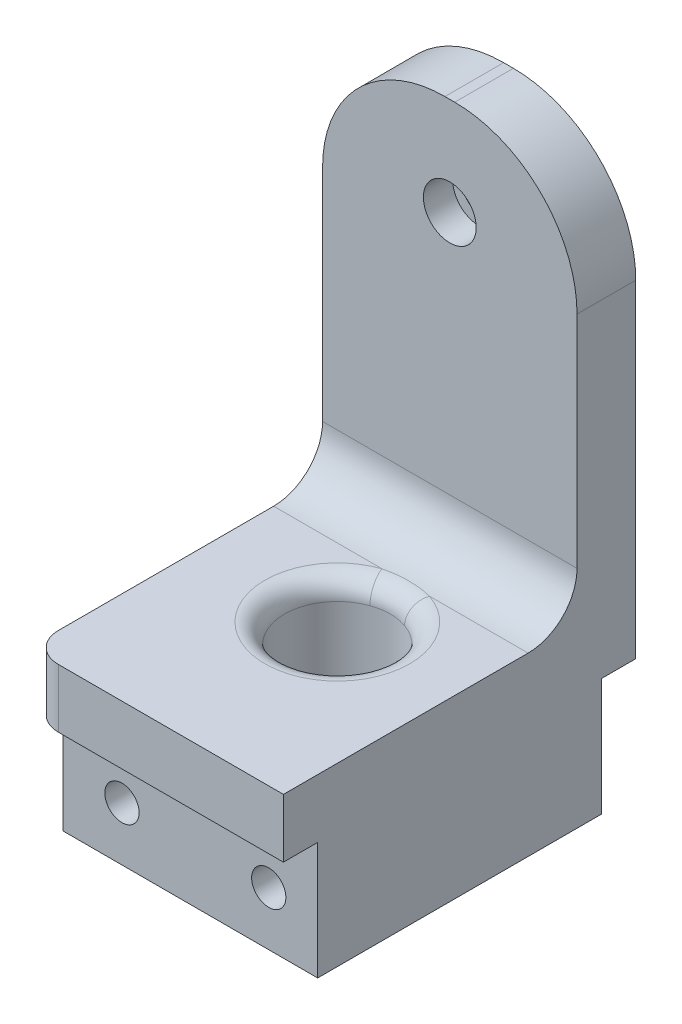
SolidWorks part; units mm, degrees
ref_plane "Front Plane" through (0, 0, 0) normal (0, 0, 1) x (1, 0, 0)
ref_plane "Top Plane" through (0, 0, 0) normal (0, 1, 0) x (1, 0, 0)
ref_plane "Right Plane" through (0, 0, 0) normal (1, 0, 0) x (0, 0, -1)
sketch "Sketch1" plane through (0, -44, 0) normal (0, 1, 0) x (1, 0, 0)
  line L0 (50.2641, 25) -> (50.2641, 28) construction
  line L1 (50.2641, -8) -> (50.2641, 28)
  line L2 (50.2641, -8) -> (27.2641, -8) construction
  line L3 (50.2641, -8) -> (27.2641, -8)
  line L4 (24.2641, -5) -> (24.2641, 25)
  line L5 (27.2641, 28) -> (50.2641, 28)
  arc A0 (27.2641, 28) -> (24.2641, 25) centre (27.2641, 25) ccw construction
  arc A1 (24.2641, -5) -> (27.2641, -8) centre (27.2641, -5) ccw construction
  arc A2 (27.2641, 28) -> (24.2641, 25) centre (27.2641, 25) ccw
  arc A3 (24.2641, -5) -> (27.2641, -8) centre (27.2641, -5) ccw
extrude "Boss-Extrude1" add sketch "Sketch1" along normal blind 6
sketch "Sketch2" plane through (0, -38, 0) normal (0, 1, 0) x (1, 0, 0)
  line L0 (24.2641, 25) -> (24.2641, -5) construction
  line L1 (50.2641, 28) -> (24.2641, 28)
  line L2 (50.2641, 28) -> (50.2641, 22)
  line L3 (50.2641, 22) -> (24.2641, 22)
  line L4 (24.2641, 28) -> (24.2641, 22)
  dimension "D1" = 6
extrude "Boss-Extrude2" add sketch "Sketch2" along normal blind 40
fillet "Fillet1" radius 12.5 2 edges at (24.2641, 2, -25) (50.2641, 2, -25)
sketch "Sketch3" plane through (0, 0, -22) normal (0, 0, 1) x (1, 0, 0)
  circle A0 centre (37.2641, -8) radius 2.7
extrude "Cut-Extrude1" cut sketch "Sketch3" against normal through all
sketch "Sketch4" plane through (0, -44, 0) normal (0, -1, 0) x (1, 0, 0)
  line L0 (24.2641, 5) -> (24.2641, -25) construction
  line L2 (24.2641, 4.5) -> (24.2641, -24.5)
  line L3 (50.2641, 4.5) -> (50.2641, -24.5)
  line L5 (24.2641, -25) -> (50.2641, -25) construction
  line L6 (50.2641, -24.5) -> (24.2641, -24.5)
  line L8 (24.2641, 4.5) -> (50.2641, 4.5)
  line L9 (50.2641, 5) -> (24.2641, 5) construction
  dimension "D1" = 0.5
  dimension "D2" = 0.5
extrude "Boss-Extrude3" add sketch "Sketch4" along normal blind 12
fillet "Fillet2" radius 5 1 edges at (37.2641, -38, -22)
sketch "Sketch5" plane through (0, 0, -24.5) normal (0, 0, -1) x (-1, 0, 0)
  circle A0 centre (-45.2641, -50.5) radius 1.75
  circle A1 centre (-30.2641, -50.5) radius 1.75
extrude "Cut-Extrude2" cut sketch "Sketch5" against normal through all
sketch "Sketch6" plane through (0, -38, 0) normal (0, -1, 0) x (1, 0, 0)
  line L2 (24.2641, -28) -> (27.2641, -28)
  line L3 (24.2641, -25) -> (24.2641, -28)
  line L4 (24.2641, -28) -> (27.2641, -28)
  line L5 (24.2641, -25) -> (24.2641, -28)
  arc A1 (24.2641, -25) -> (27.2641, -28) centre (27.2641, -25) ccw
  arc A2 (24.2641, -25) -> (27.2641, -28) centre (27.2641, -25) ccw
  dimension "D1" = 0
extrude "Cut-Extrude3" cut sketch "Sketch6" against normal through all
sketch "Sketch7" plane through (0, -56, 0) normal (0, -1, 0) x (1, 0, 0)
  line L0 (32.0141, 4.5) -> (28.5141, 4.5) construction
  line L1 (47.0141, 4.5) -> (43.5141, 4.5) construction
  line L2 (32.0141, 4.5) -> (28.5141, 4.5) construction
  line L3 (47.0141, 4.5) -> (43.5141, 4.5) construction
  line L4 (28.5141, 4.5) -> (28.5141, -10.0084) construction
  line L5 (47.0141, 4.5) -> (47.0141, -10.0084) construction
  line L6 (28.5141, -10.0084) -> (47.0141, -10.0084) construction
  circle A0 centre (37.7641, -10.0084) radius 5.4
extrude "Cut-Extrude4" cut sketch "Sketch7" against normal up to surface (18 mm away) up to face at (35.1398, -38, -2.4757)
fillet "Fillet3" radius 2 2 edges at (43.1641, -56, -10.0084) (32.3641, -38, -10.0084)
sketch "Sketch8" plane through (0, 0, -28) normal (0, 0, -1) x (-1, 0, 0)
  circle A0 centre (-37.2641, -8) radius 2.7 construction
  circle A1 centre (-37.2641, -8) radius 2.7
  circle A2 centre (-37.2641, -8) radius 1.6
extrude "Boss-Extrude4" add sketch "Sketch8" against normal blind 3
